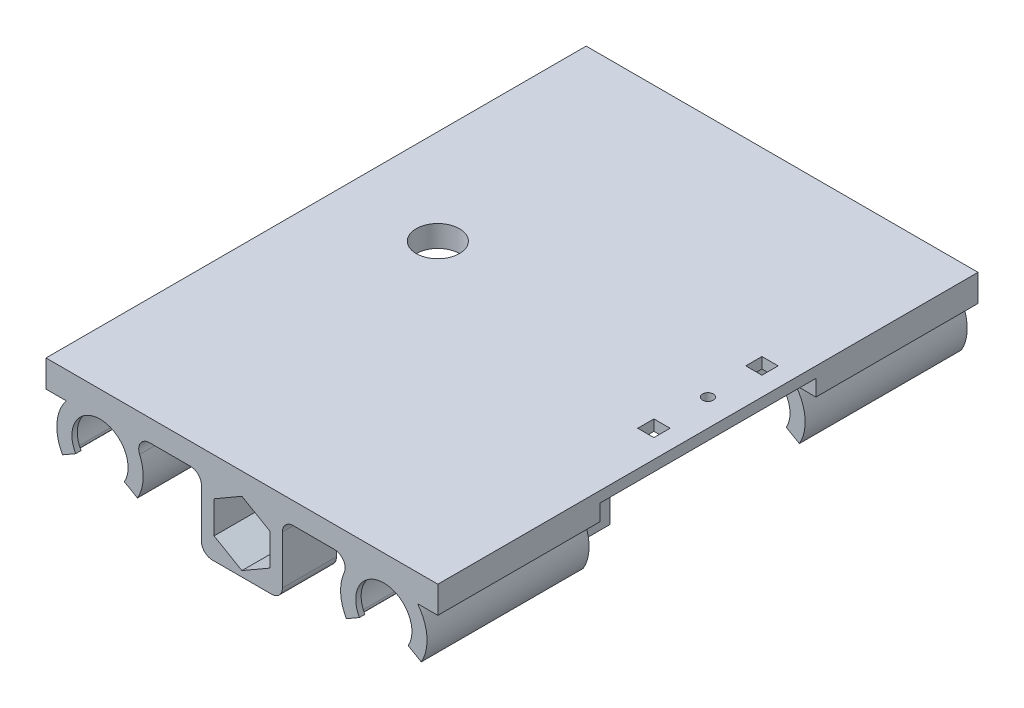
SolidWorks part; units mm, degrees
ref_plane "Front Plane" through (0, 0, 0) normal (0, 0, 1) x (1, 0, 0)
ref_plane "Top Plane" through (0, 0, 0) normal (0, 1, 0) x (1, 0, 0)
ref_plane "Right Plane" through (0, 0, 0) normal (1, 0, 0) x (0, 0, -1)
sketch "Sketch1" plane through (0, 0, 0) normal (0, 0, 1) x (1, 0, 0)
  line L0 (0, 0) -> (19.9916, 0) construction
  line L1 (19.9916, 0) -> (-22.0915, 0) construction
  line L2 (0, 0) -> (-8.7988, -5.08)
  line L3 (-8.7988, -5.08) -> (0, 0)
  line L4 (0, 0) -> (8.7988, -5.08)
  circle A0 centre (0, 0) radius 7.62
  circle A1 centre (0, 0) radius 10.16
  dimension "D1" = 15.24
  dimension "D2" = 30
  dimension "D3" = 30
extrude "Boss-Extrude1" add sketch "Sketch1" along normal blind 38.1 contours L4 A1 L3 A0 region at (-7.826, -4.225, 0)
ref_plane "Plane1" through (0, 0, -25.4) normal (0, 0, 1) x (1, 0, 0)
ref_plane "Plane2" through (0, 10.16, 0) normal (0, 1, 0) x (1, 0, 0)
sketch "Sketch2" plane through (0, 10.16, 0) normal (0, 1, 0) x (1, 0, 0)
  line L0 (0, 0) -> (0, -28.4558) construction
  line L2 (0, -22.2211) -> (66.7283, -22.2211)
  line L3 (0, -22.2211) -> (0, 104.7789)
  line L4 (0, 104.7789) -> (66.7283, 104.7789)
  line L5 (66.7283, -22.2211) -> (66.7283, 104.7789)
  dimension "D1" = 127
extrude "Boss-Extrude2" add sketch "Sketch2" against normal blind 2.54
mirror "Mirror2" about plane through (0, 0, -25.4) normal (0, 0, 1) of "Boss-Extrude1"
sketch "Sketch3" plane through (0, 10.16, 0) normal (0, 1, 0) x (1, 0, 0)
  line L0 (33.3642, 104.7789) -> (33.3642, -22.2211) construction
  line L1 (66.7283, 104.7789) -> (0, 104.7789) construction
  line L2 (0, -22.2211) -> (66.7283, -22.2211) construction
ref_plane "Plane3" through (33.3642, 0, 0) normal (1, 0, 0) x (0, 0, -1)
mirror "Mirror3" about plane through (33.3642, 0, 0) normal (1, 0, 0) of "Mirror2"
sketch "Sketch4" plane through (0, 10.16, 0) normal (0, 1, 0) x (1, 0, 0)
  line L0 (0, -22.2211) -> (66.7283, 104.7789) construction
  line L1 (0, -22.2211) -> (66.7283, -22.2211) construction
  line L2 (79.4283, -22.2211) -> (-12.7, -22.2211)
  line L3 (79.4283, -22.2211) -> (79.4283, 104.7789)
  line L4 (79.4283, 104.7789) -> (-12.7, 104.7789)
  line L5 (-12.7, -22.2211) -> (-12.7, 104.7789)
  line L6 (79.4283, -22.2211) -> (-12.7, 104.7789) construction
  line L7 (79.4283, 104.7789) -> (-12.7, -22.2211) construction
  line L8 (0, 50.8) -> (0, 0) construction
  line L9 (66.7283, -22.2211) -> (66.7283, 0) construction
  line L10 (66.7283, 104.7789) -> (0, 104.7789) construction
  point P3 (33.3642, 41.2789)
  dimension "D1" = 0
  dimension "D2" = 12.7
  dimension "D3" = 12.7
  dimension "D4" = 0
extrude "Boss-Extrude3" add sketch "Sketch4" along normal blind 2.54
chamfer "Chamfer1" distance 2.54 angle 45 2 edges at (66.7283, 7.62, -25.4) (0, 7.62, -25.4)
fillet "Fillet1" radius 2.54 4 edges at (60.0081, 7.62, -69.85) (6.7202, 7.62, -69.85) (60.0081, 7.62, 11.1105) (6.7202, 7.62, 11.1105)
sketch "Sketch5" plane through (0, 0, -104.7789) normal (0, 0, -1) x (-1, 0, 0)
  line L0 (-79.4283, 12.7) -> (-79.4283, 10.16)
  line L1 (-79.4283, 10.16) -> (-66.7283, 10.16)
  line L2 (-66.7283, 10.16) -> (-66.7283, 7.62)
  line L3 (-66.7283, 7.62) -> (0, 7.62)
  line L4 (0, 7.62) -> (0, 10.16)
  line L5 (0, 10.16) -> (12.7, 10.16)
  line L6 (12.7, 10.16) -> (12.7, 12.7)
  line L7 (12.7, 12.7) -> (-79.4283, 12.7)
extrude "Cut-Extrude1" cut sketch "Sketch5" against normal up to surface (15.8789 mm away) up to face at (72.5026, 3.3337, -88.9)
sketch "Sketch6" plane through (0, 0, 22.2211) normal (0, 0, 1) x (1, 0, 0)
  line L0 (-12.7, 10.16) -> (-12.7, 12.7)
  line L1 (-12.7, 12.7) -> (79.4283, 12.7)
  line L2 (79.4283, 12.7) -> (79.4283, 10.16)
  line L3 (79.4283, 10.16) -> (66.7283, 10.16)
  line L4 (66.7283, 10.16) -> (57.4165, 4.064)
  line L5 (55.0886, 7.62) -> (11.6397, 7.62)
  line L6 (-12.7, 10.16) -> (0, 10.16)
  line L7 (0, 10.16) -> (9.3118, 4.064)
  arc A0 (9.3118, 4.064) -> (11.6397, 7.62) centre (11.6397, 5.08) cw
  arc A1 (57.4165, 4.064) -> (55.0886, 7.62) centre (55.0886, 5.08) ccw
extrude "Boss-Extrude4" add sketch "Sketch6" along normal up to surface (15.8789 mm away) up to face at (0, 2.2225, 38.1)
sketch "Sketch7" plane through (0, 0, -88.9) normal (0, 0, -1) x (-1, 0, 0)
  circle A0 centre (0, 0) radius 7.62
  circle A1 centre (0, 0) radius 7.747
  dimension "D1" = 15.24
  dimension "D2" = 15.494
extrude "Cut-Extrude2" cut sketch "Sketch7" against normal blind 157.734
sketch "Sketch8" plane through (0, 0, -88.9) normal (0, 0, -1) x (-1, 0, 0)
  circle A0 centre (0, 0) radius 7.747
extrude "Boss-Extrude6" add sketch "Sketch8" against normal blind 1.27
ref_plane "Plane4" through (0, 0, -69.85) normal (0, 0, 1) x (1, 0, 0)
mirror "Mirror4" about plane through (0, 0, -69.85) normal (0, 0, 1) of "Boss-Extrude6"
ref_plane "Plane5" through (0, 0, -25.4) normal (0, 0, 1) x (1, 0, 0)
mirror "Mirror5" about plane through (0, 0, -25.4) normal (0, 0, 1) of "Mirror4"
sketch "Sketch10" plane through (0, 0, -88.9) normal (0, 0, -1) x (-1, 0, 0)
  line L0 (6.7091, -3.8735) -> (5.7192, -3.302)
  line L1 (-6.7091, -3.8735) -> (-5.7192, -3.302)
  circle A0 centre (0, 0) radius 6.604
  arc M2 (-6.7091, -3.8735) -> (6.7091, -3.8735) centre (0, 0) ccw
extrude "Cut-Extrude3" cut sketch "Sketch10" against normal blind 177.292 contours A0 L1 L0 M2 | A0 region at (0, -7.6056, -88.9) region at (0, 0, -88.9)
ref_plane "Plane6" through (33.3642, 0, 0) normal (-1, 0, 0) x (0, 0, 1)
mirror "Mirror8" about plane through (33.3642, 0, 0) normal (-1, 0, 0) of "Mirror4", "Mirror5"
mirror "Mirror9" about plane through (33.3642, 0, 0) normal (-1, 0, 0) of "Cut-Extrude3"
fillet "Fillet3" radius 0.635 8 edges at (73.3275, -3.81, 19.05) (60.1292, -3.81, 19.05) (60.1292, -3.81, -69.85) (73.3275, -3.81, -69.85) (6.7091, -3.8735, -69.85) (-6.7091, -3.8735, -69.85) (6.7091, -3.8735, 19.05) (-6.7091, -3.8735, 19.05)
sketch "Sketch11" plane through (-12.7, 0, 0) normal (-1, 0, 0) x (0, 0, 1)
  line L1 (38.1, 12.7) -> (0, 12.7)
  line L2 (38.1, 12.7) -> (38.1, 6.35)
  line L3 (38.1, 6.35) -> (0, 6.35)
  line L4 (0, 12.7) -> (0, 6.35)
  dimension "D1" = 6.35
extrude "Boss-Extrude7" add sketch "Sketch11" against normal up to body
mirror "Mirror11" about plane through (0, 0, -25.4) normal (0, 0, 1) of "Boss-Extrude7"
mirror "Mirror12" about plane through (33.3642, 0, 0) normal (-1, 0, 0) of "Mirror11"
sketch "Sketch12" plane through (0, 7.62, 0) normal (0, -1, 0) x (1, 0, 0)
  line L0 (33.3642, 38.1) -> (33.3642, -88.9) construction
  line L1 (11.6397, 38.1) -> (55.0886, 38.1) construction
  line L2 (11.6397, -88.9) -> (55.0886, -88.9) construction
  line L3 (66.7283, 38.1) -> (66.7283, -88.9)
  line L4 (79.4283, -88.9) -> (-12.7, -88.9) construction
  line L5 (79.4283, 38.1) -> (79.4283, -88.9) construction
  line L6 (9.5783, -31.75) -> (128.2092, -31.75) construction
  line L7 (73.0783, -31.75) -> (73.0783, 0.8928) construction
  line L8 (73.0783, 0.8928) -> (73.0783, -73.0235) construction
  line L10 (71.1733, -46.355) -> (74.9833, -46.355)
  line L11 (71.1733, -46.355) -> (71.1733, -42.545)
  line L12 (71.1733, -42.545) -> (74.9833, -42.545)
  line L13 (74.9833, -46.355) -> (74.9833, -42.545)
  line L14 (71.1733, -46.355) -> (74.9833, -42.545) construction
  line L15 (71.1733, -42.545) -> (74.9833, -46.355) construction
  line L16 (71.1733, -20.955) -> (74.9833, -20.955)
  line L17 (71.1733, -20.955) -> (71.1733, -17.145)
  line L18 (71.1733, -17.145) -> (74.9833, -17.145)
  line L19 (74.9833, -20.955) -> (74.9833, -17.145)
  line L20 (71.1733, -20.955) -> (74.9833, -17.145) construction
  line L21 (71.1733, -17.145) -> (74.9833, -20.955) construction
  circle A0 centre (9.5783, -31.75) radius 5.08
  circle A1 centre (73.0783, -31.75) radius 1.27
  point P6 (9.5783, -31.75)
  point P18 (73.0783, -44.45)
  point P25 (73.0783, -19.05)
  dimension "D4" = 2.54
  dimension "D12" = 10.16
  dimension "D1" = 57.15
  dimension "D2" = 57.15
  dimension "D3" = 12.7
  dimension "D5" = 6.35
  dimension "D6" = 3.81
  dimension "D7" = 3.81
  dimension "D8" = 3.81
  dimension "D9" = 3.81
  dimension "D10" = 12.7
  dimension "D11" = 12.7
extrude "Cut-Extrude4" cut sketch "Sketch12" against normal blind 30.456 contours A0 | L10 L13 L12 L11 | A1 | L16 L19 L18 L17 region at (73.0783, 7.62, -44.45) region at (73.0783, 7.62, -19.05) region at (9.5783, 7.62, -31.75) region at (73.0783, 7.62, -31.75)
sketch "Sketch13" plane through (-12.7, 0, 0) normal (-1, 0, 0) x (0, 0, 1)
  line L0 (-25.4, 12.7) -> (-25.4, -32.9309) construction
  line L1 (-88.9, 12.7) -> (38.1, 12.7) construction
sketch "Sketch14" plane through (0, 0, 38.1) normal (0, 0, 1) x (1, 0, 0)
  line L0 (23.8395, -8.89) -> (23.8395, 7.62)
  line L1 (23.8395, -8.89) -> (42.8895, -8.89)
  line L2 (23.8395, 7.62) -> (42.8895, 7.62)
  line L3 (42.8895, -8.89) -> (42.8895, 7.62)
  line L4 (23.8395, -8.89) -> (42.8895, 7.62) construction
  line L5 (23.8395, 7.62) -> (42.8895, -8.89) construction
  line L6 (33.3645, 0) -> (33.3645, -27.078) construction
  line L7 (33.3645, -27.078) -> (33.2435, -28.2) construction
  line L8 (61.4375, -28.2) -> (5.0495, -28.2) construction
  line L9 (11.6397, 7.62) -> (55.0886, 7.62) construction
  line L11 (33.3645, 7.5633) -> (26.8145, 3.7816)
  line L12 (26.8145, 3.7816) -> (26.8145, -3.7816)
  line L13 (26.8145, -3.7816) -> (33.3645, -7.5633)
  line L14 (33.3645, -7.5633) -> (39.9145, -3.7816)
  line L15 (39.9145, -3.7816) -> (39.9145, 3.7816)
  line L16 (39.9145, 3.7816) -> (33.3645, 7.5633)
  circle A0 centre (33.3645, 0) radius 6.55 construction
  point P0 (33.3645, 0)
  point P1 (33.3645, -0.635)
  dimension "D5" = 13.1
  dimension "D1" = 19.05
  dimension "D2" = 16.51
  dimension "D3" = 2.8353
  dimension "D4" = 0
  dimension "D6" = 0
  dimension "D7" = 0
extrude "Boss-Extrude9" add sketch "Sketch14" against normal blind 12.7
fillet "Fillet5" radius 2.54 4 edges at (23.8395, 7.62, 31.75) (23.8395, -8.89, 31.75) (42.8895, -8.89, 31.75) (42.8895, 7.62, 31.75)
ref_plane "Plane8" through (0, 0, -25.4) normal (0, 0, 1) x (1, 0, 0)
mirror "Mirror14" about plane through (0, 0, -25.4) normal (0, 0, 1) of "Boss-Extrude9", "Fillet5"
sketch "Sketch15" plane through (0, 7.62, 0) normal (0, -1, 0) x (1, 0, 0)
  line L0 (2.54, -25.4) -> (64.1883, -25.4) construction
  line L1 (2.54, 0) -> (2.54, -50.8) construction
  line L2 (64.1883, -50.8) -> (64.1883, 0) construction
  line L3 (22.3838, -30.1457) -> (22.3838, -20.6375) construction
  line L4 (46.8846, -34.925) -> (19.8438, -34.925)
  line L5 (46.8846, -34.925) -> (46.8846, -15.875)
  line L6 (46.8846, -15.875) -> (19.8438, -15.875)
  line L7 (19.8438, -34.925) -> (19.8438, -15.875)
  line L8 (46.8846, -34.925) -> (19.8438, -15.875) construction
  line L9 (46.8846, -15.875) -> (19.8438, -34.925) construction
  point P6 (33.3642, -25.4)
  dimension "D1" = 2.54
  dimension "D2" = 19.05
extrude "Boss-Extrude10" add sketch "Sketch15" along normal blind 35.56
sketch "Sketch16" plane through (0, 0, -34.925) normal (0, 0, -1) x (-1, 0, 0)
  circle A0 centre (-33.3645, 0) radius 5.08
extrude "Cut-Extrude5" cut sketch "Sketch16" against normal blind 35.56
sketch "Sketch17" plane through (19.8438, 0, 0) normal (-1, 0, 0) x (0, 0, 1)
  circle A0 centre (-25.4, -20.6925) radius 4.6355
extrude "Cut-Extrude6" cut sketch "Sketch17" against normal blind 40.386
chamfer "Chamfer2" distance 10.16 angle 45 2 edges at (33.3642, 7.62, -34.925) (33.3642, 7.62, -15.875)
